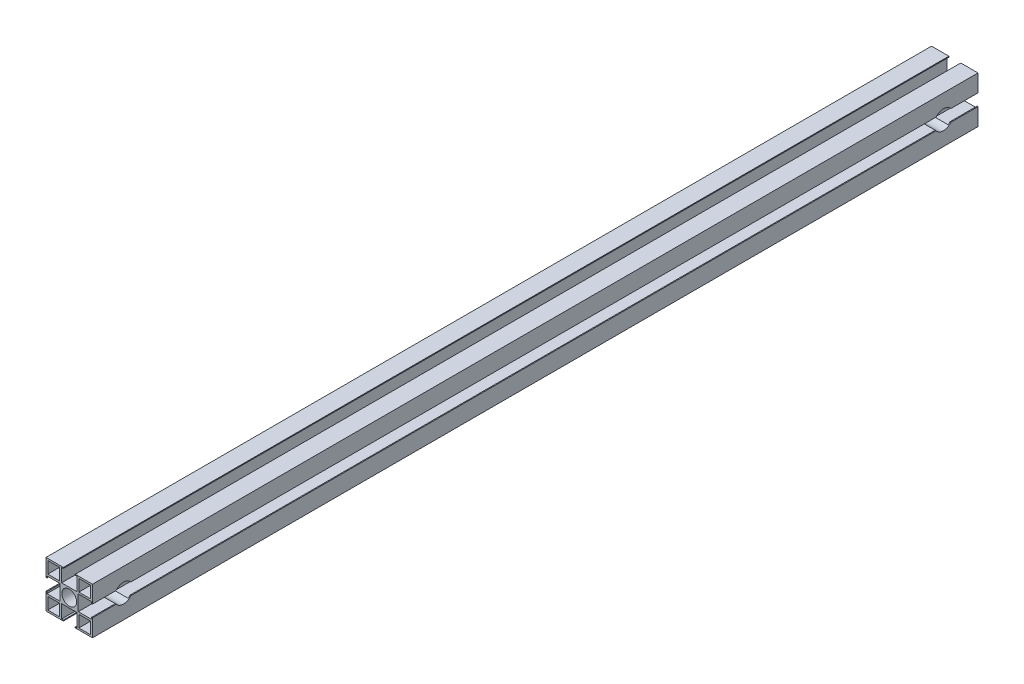
SolidWorks part; units mm, degrees
ref_plane "Front Plane" through (0, 0, 0) normal (0, 0, 1) x (1, 0, 0)
ref_plane "Top Plane" through (0, 0, 0) normal (0, 1, 0) x (1, 0, 0)
ref_plane "Right Plane" through (0, 0, 0) normal (1, 0, 0) x (0, 0, -1)
sketch "Sketch1" plane through (0, 0, 0) normal (0, 0, 1) x (1, 0, 0)
  line L1 (-19.939, 19.939) -> (19.939, 19.939)
  line L2 (-19.939, 19.939) -> (-19.939, -19.939)
  line L3 (-19.939, -19.939) -> (19.939, -19.939)
  line L4 (19.939, 19.939) -> (19.939, -19.939)
  dimension "D1" = 39.878
  dimension "D2" = 39.878
  dimension "D3" = 19.939
  dimension "D4" = 19.939
extrude "Boss-Extrude1" add sketch "Sketch1" along normal blind 759.968 contours L1 L4 L3 L2
sketch "Sketch2" plane through (0, 0, 0) normal (0, 0, -1) x (-1, 0, 0)
  line L0 (0, 0) -> (0, 19.939) construction
  line L2 (-6.6421, 19.1663) -> (-6.6421, 7.7363)
  line L3 (-6.6421, 7.7363) -> (6.5659, 7.7363)
  line L4 (6.5659, 19.1663) -> (6.5659, 7.7363)
  line L5 (19.939, 19.939) -> (-19.939, 19.939) construction
  line L6 (-6.6421, 19.1663) -> (-5.1181, 19.1663)
  line L7 (-5.1181, 19.1663) -> (-5.1181, 19.939)
  line L8 (-5.1181, 19.939) -> (5.0419, 19.939)
  line L9 (5.0419, 19.939) -> (5.0419, 19.1663)
  line L10 (5.0419, 19.1663) -> (6.5659, 19.1663)
  dimension "D1" = 11.43
  dimension "D2" = 6.6421
  dimension "D3" = 1.524
  dimension "D4" = 1.524
  dimension "D5" = 13.208
  dimension "D6" = 11.43
extrude "Cut-Extrude1" cut sketch "Sketch2" against normal blind 759.968
ref_plane "Plane1" through (0, 0, 0) normal (-0.7071, 0.7071, 0) x (0, 0, 1)
ref_plane "Plane2" through (0, 0, 0) normal (-0.7071, -0.7071, 0) x (-0.7071, 0.7071, 0)
ref_plane "Plane3" through (0, 0, 0) normal (0, 1, 0) x (1, 0, 0)
mirror "Mirror1" about plane through (0, 0, 0) normal (0, 1, 0) of "Cut-Extrude1"
mirror "Mirror2" about plane through (0, 0, 0) normal (-0.7071, 0.7071, 0) of "Cut-Extrude1"
mirror "Mirror4" about plane through (0, 0, 0) normal (-0.7071, -0.7071, 0) of "Cut-Extrude1"
sketch "Sketch3" plane through (0, 0, 0) normal (0, 0, -1) x (-1, 0, 0)
  line L1 (-18.415, 18.415) -> (-8.255, 18.415)
  line L2 (-18.415, 18.415) -> (-18.415, 8.255)
  line L3 (-18.415, 8.255) -> (-8.255, 8.255)
  line L4 (-8.255, 18.415) -> (-8.255, 8.255)
  line L5 (-18.415, -8.255) -> (-8.255, -8.255)
  line L6 (-18.415, -8.255) -> (-18.415, -18.415)
  line L7 (-18.415, -18.415) -> (-8.255, -18.415)
  line L8 (-8.255, -8.255) -> (-8.255, -18.415)
  line L9 (8.255, 18.415) -> (18.415, 18.415)
  line L10 (8.255, 18.415) -> (8.255, 8.255)
  line L11 (8.255, 8.255) -> (18.415, 8.255)
  line L12 (18.415, 18.415) -> (18.415, 8.255)
  line L13 (8.255, -8.255) -> (18.415, -8.255)
  line L14 (8.255, -8.255) -> (8.255, -18.415)
  line L15 (8.255, -18.415) -> (18.415, -18.415)
  line L16 (18.415, -8.255) -> (18.415, -18.415)
  line L17 (-19.939, 19.939) -> (19.939, -19.939) construction
  line L18 (-19.939, -19.939) -> (19.939, 19.939) construction
  line L19 (-19.1663, 6.6421) -> (-19.939, 6.6421) construction
  line L20 (-19.939, 19.939) -> (-19.939, 5.1181) construction
  line L21 (-19.939, 6.6421) -> (-6.6421, 19.939) construction
  line L22 (-5.1181, 19.939) -> (-19.939, 19.939) construction
  dimension "D1" = 10.16
  dimension "D2" = 10.16
  dimension "D3" = 1.524
  dimension "D4" = 1.524
  dimension "D5" = 10.16
  dimension "D6" = 10.16
  dimension "D7" = 1.524
  dimension "D8" = 1.524
  dimension "D9" = 10.16
  dimension "D10" = 10.16
  dimension "D11" = 1.524
  dimension "D12" = 1.524
  dimension "D13" = 10.16
  dimension "D14" = 10.16
  dimension "D15" = 1.524
  dimension "D16" = 1.524
extrude "Cut-Extrude2" cut sketch "Sketch3" against normal blind 759.968
sketch "Sketch4" plane through (0, 0, 0) normal (0, 0, -1) x (-1, 0, 0)
  circle A0 centre (0, 0) radius 6.35
extrude "Cut-Extrude3" cut sketch "Sketch4" against normal blind 759.968
sketch "Sketch5" plane through (7.7363, 0, 0) normal (1, 0, 0) x (0, 0, -1)
  circle A0 centre (-733.3607, 0.0381) radius 8.128
  circle A1 centre (-29.6098, 0) radius 8.128
extrude "Cut-Extrude4" cut sketch "Sketch5" against normal through all
extrude "Cut-Extrude5" cut sketch "Sketch5<2>" along normal through all
sketch "Sketch5<2>" plane through (7.7363, 0, 0) normal (1, 0, 0) x (0, 0, -1) same geometry as "Sketch5"
